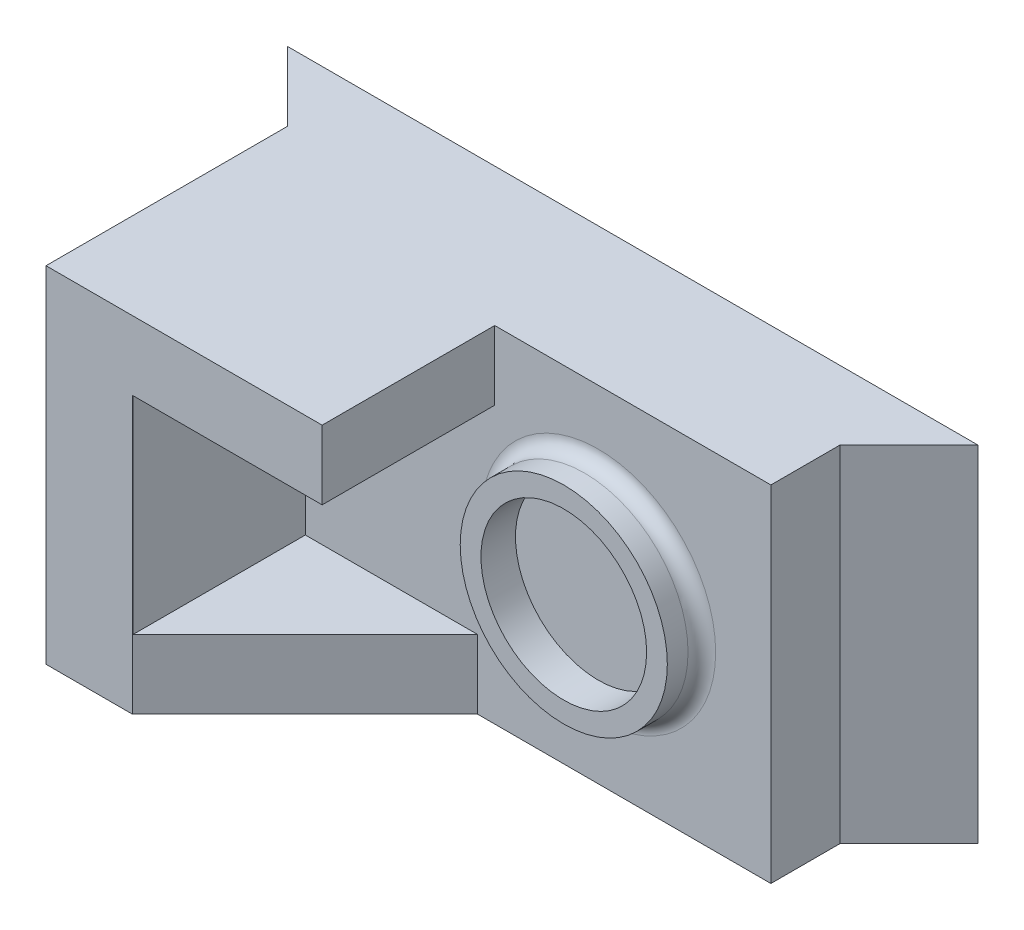
SolidWorks part; units mm, degrees
material "1060 Alloy"
ref_plane "Front Plane" through (0, 0, 0) normal (0, 0, 1) x (1, 0, 0)
ref_plane "Top Plane" through (0, 0, 0) normal (0, 1, 0) x (1, 0, 0)
ref_plane "Right Plane" through (0, 0, 0) normal (1, 0, 0) x (0, 0, -1)
sketch "Sketch1" plane through (0, 0, 0) normal (0, 0, 1) x (1, 0, 0)
  line L1 (-50, 25) -> (50, 25)
  line L2 (-50, 25) -> (-50, -25)
  line L3 (-50, -25) -> (50, -25)
  line L4 (50, 25) -> (50, -25)
  line L5 (-50, 25) -> (50, -25) construction
  line L6 (-50, -25) -> (50, 25) construction
  point P0 (0, 0)
  dimension "D1" = 100
  dimension "D2" = 50
extrude "Boss-Extrude2" add sketch "Sketch1" along normal blind 10
sketch "Sketch3" plane through (0, 0, 10) normal (0, 0, 1) x (1, 0, 0)
  line L0 (-50, 25) -> (-50, -25) construction
  line L1 (-40, 25) -> (40, 25)
  line L2 (-40, 25) -> (-40, -25)
  line L3 (-40, -25) -> (40, -25)
  line L4 (40, 25) -> (40, -25)
  line L5 (-40, 25) -> (40, -25) construction
  line L6 (-40, -25) -> (40, 25) construction
  point P0 (0, 0)
  dimension "D1" = 80
  dimension "D2" = 50
  dimension "D3" = 10
extrude "Boss-Extrude3" add sketch "Sketch3" along normal blind 10
sketch "Sketch4" plane through (0, 0, 20) normal (0, 0, 1) x (1, 0, 0)
  line L0 (-40, -25) -> (40, -25) construction
  line L1 (-40, 25) -> (0, 25)
  line L2 (-40, 25) -> (-40, -25)
  line L3 (-40, -25) -> (0, -25)
  line L4 (0, 25) -> (0, -25)
  dimension "D1" = 40
  dimension "D2" = 50
extrude "Boss-Extrude4" add sketch "Sketch4" along normal blind 25
sketch "Sketch5" plane through (0, 0, 45) normal (0, 0, 1) x (1, 0, 0)
  line L0 (-40, -25) -> (0, -25) construction
  line L1 (-27.435, 15) -> (32.565, 15)
  line L2 (-27.435, 15) -> (-27.435, -15)
  line L3 (-27.435, -15) -> (32.565, -15)
  line L4 (32.565, 15) -> (32.565, -15)
  dimension "D1" = 10
extrude "Cut-Extrude1" cut sketch "Sketch5" against normal blind 25
sketch "Sketch6" plane through (0, 0, 20) normal (0, 0, 1) x (1, 0, 0)
  line L0 (15, 25) -> (15, -25) construction
  line L1 (40, 25) -> (0, 25) construction
  line L2 (0, -25) -> (40, -25) construction
  line L3 (15, -25) -> (14.6983, -24.6512) construction
  line L4 (0, 15) -> (0, 25) construction
  line L5 (0, 0) -> (60.4871, 0) construction
  line L6 (60.4871, 0) -> (60.7888, -0.5156) construction
  line L7 (50, -25) -> (50, 25) construction
  circle A0 centre (15, 0) radius 15
  circle A1 centre (15, 0) radius 12
  dimension "D4" = 30
  dimension "D5" = 24
  dimension "D1" = 15
  dimension "D2" = 25
  dimension "D3" = 35
extrude "Boss-Extrude5" add sketch "Sketch6" along normal blind 5
chamfer "Chamfer2" distance 10 angle 45 1 edges at (50, 0, 10)
chamfer "Chamfer3" distance 10 angle 45 1 edges at (-50, 0, 10)
fillet "Fillet3" radius 2 1 edges at (30, 0, 20)
chamfer "Chamfer6" distance 27.5 angle 45 1 edges at (0, -20, 45)
